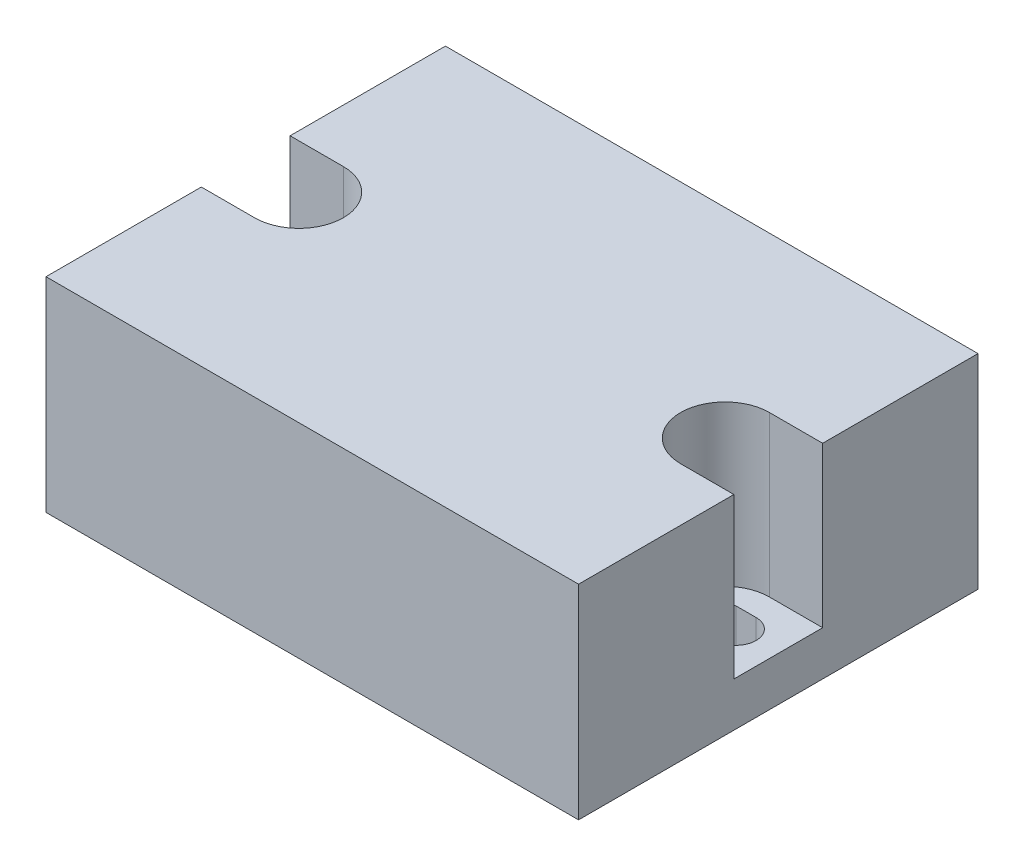
SolidWorks part; units mm, degrees
ref_plane "Front Plane" through (0, 0, 0) normal (0, 0, 1) x (1, 0, 0)
ref_plane "Top Plane" through (0, 0, 0) normal (0, 1, 0) x (1, 0, 0)
ref_plane "Right Plane" through (0, 0, 0) normal (1, 0, 0) x (0, 0, -1)
sketch "Sketch1" plane through (0, 0, 0) normal (0, 1, 0) x (1, 0, 0)
  line L1 (-30, -22.5) -> (30, -22.5)
  line L2 (-30, -22.5) -> (-30, 22.5)
  line L3 (-30, 22.5) -> (30, 22.5)
  line L4 (30, -22.5) -> (30, 22.5)
  line L5 (-30, -22.5) -> (30, 22.5) construction
  line L6 (-30, 22.5) -> (30, -22.5) construction
  point P0 (0, 0)
  dimension "D1" = 45
  dimension "D2" = 60
extrude "Boss-Extrude1" add sketch "Sketch1" along normal blind 23
sketch "Sketch2" plane through (0, 23, 0) normal (0, 1, 0) x (1, 0, 0)
  line L0 (24, 0) -> (38.957, 0) construction
  line L1 (24, 5) -> (38.957, 5)
  line L2 (24, -5) -> (38.957, -5)
  line L3 (0, 0) -> (0, 44.5269) construction
  line L4 (-24, 0) -> (-38.957, 0) construction
  line L5 (-24, 5) -> (-38.957, 5)
  line L6 (-24, -5) -> (-38.957, -5)
  arc A0 (24, 5) -> (24, -5) centre (24, 0) ccw
  arc A1 (38.957, -5) -> (38.957, 5) centre (38.957, 0) ccw
  arc A2 (-24, 5) -> (-24, -5) centre (-24, 0) cw
  arc A3 (-38.957, -5) -> (-38.957, 5) centre (-38.957, 0) cw
  point P3 (31.4785, 0)
  point P12 (-31.4785, 0)
  dimension "D2" = 38
  dimension "D1" = 10
extrude "Cut-Extrude1" cut sketch "Sketch2" against normal offset from surface (18 mm away) 5 up to face at (0, 0, 0)
sketch "Sketch3" plane through (0, 5, 0) normal (0, 1, 0) x (1, 0, 0)
  line L0 (23, 0) -> (25.25, 0) construction
  line L1 (23, 2.25) -> (25.25, 2.25)
  line L2 (23, -2.25) -> (25.25, -2.25)
  line L3 (0, 0) -> (0, 34.0454) construction
  line L4 (-23, 0) -> (-25.25, 0) construction
  line L5 (-23, 2.25) -> (-25.25, 2.25)
  line L6 (-23, -2.25) -> (-25.25, -2.25)
  arc A0 (23, 2.25) -> (23, -2.25) centre (23, 0) ccw
  arc A1 (25.25, -2.25) -> (25.25, 2.25) centre (25.25, 0) ccw
  arc A2 (-23, 2.25) -> (-23, -2.25) centre (-23, 0) cw
  arc A3 (-25.25, -2.25) -> (-25.25, 2.25) centre (-25.25, 0) cw
  point P3 (24.125, 0)
  point P12 (-24.125, 0)
  point P17 (0, 0)
  dimension "D2" = 41.5
  dimension "D3" = 55
  dimension "D1" = 4.5
extrude "Cut-Extrude2" cut sketch "Sketch3" against normal blind 10
